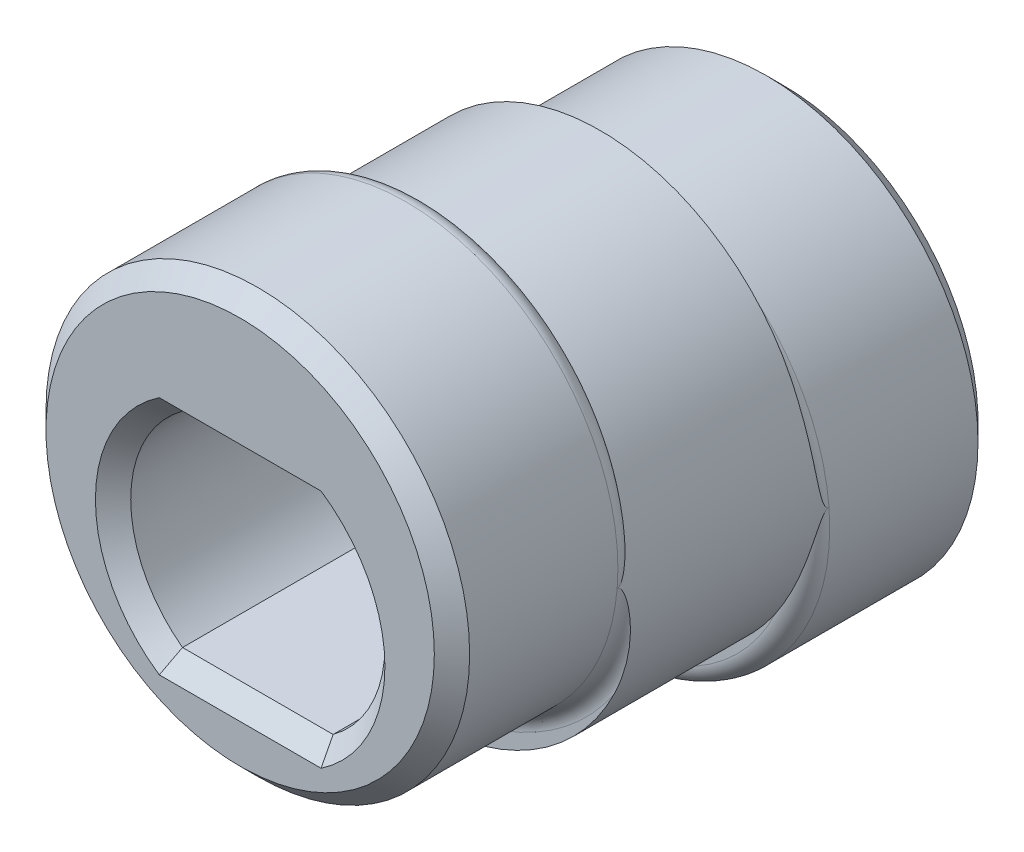
SolidWorks part; units mm, degrees
material "Polylactic Acid (PLA)"
ref_plane "Front Plane" through (0, 0, 0) normal (0, 0, 1) x (1, 0, 0)
ref_plane "Top Plane" through (0, 0, 0) normal (0, 1, 0) x (1, 0, 0)
ref_plane "Right Plane" through (0, 0, 0) normal (1, 0, 0) x (0, 0, -1)
sketch "Sketch6" plane through (0, 0, 0) normal (0, 0, 1) x (1, 0, 0)
  circle A0 centre (0, 0) radius 6
  dimension "D1" = 12
extrude "Boss-Extrude4" add sketch "Sketch6" along normal mid plane 5
sketch "Sketch7" plane through (0, 0, 2.5) normal (0, 0, 1) x (1, 0, 0)
  circle A0 centre (0, 1) radius 6
  dimension "D1" = 12
  dimension "D2" = 1
extrude "Boss-Extrude5" add sketch "Sketch7" along normal blind 5.2
sketch "Sketch8" plane through (0, 0, -2.5) normal (0, 0, -1) x (-1, 0, 0)
  circle A0 centre (0, -1) radius 6
  dimension "D1" = 12
  dimension "D2" = 1
extrude "Boss-Extrude6" add sketch "Sketch8" along normal blind 5.2
sketch "Sketch11" plane through (0, 0, 2.5) normal (0, 0, 1) x (1, 0, 0)
  line L0 (-2.1331, -2.9) -> (2.1331, -2.9)
  line L1 (-1.9975, -2.5) -> (1.9975, -2.5) construction
  line L2 (-1.9975, -2.5) -> (-1.9975, 2.5) construction
  line L3 (-1.9975, 2.5) -> (1.9975, 2.5) construction
  line L4 (1.9975, -2.5) -> (1.9975, 2.5) construction
  line L5 (-1.9975, -2.5) -> (1.9975, 2.5) construction
  line L6 (-1.9975, 2.5) -> (1.9975, -2.5) construction
  line L7 (-2.1331, 2.9) -> (2.1331, 2.9)
  arc A0 (-1.9975, 2.5) -> (-1.9975, -2.5) centre (0, 0) ccw construction
  arc A1 (1.9975, -2.5) -> (1.9975, 2.5) centre (0, 0) ccw construction
  arc A2 (2.1331, -2.9) -> (2.1331, 2.9) centre (0, 0) ccw
  arc A3 (-2.1331, 2.9) -> (-2.1331, -2.9) centre (0, 0) ccw
  dimension "D1" = 6.4
  dimension "D2" = 2.5
  dimension "D3" = 0.4
extrude "Cut-Extrude1" cut sketch "Sketch11" against normal through all both and the other way through all
fillet "Fillet1" radius 0.5 2 edges at (0, -5, 2.5) (0, 5, -2.5)
fillet "Fillet2" radius 0.5 2 edges at (0, -7, -2.5) (0, 7, 2.5)
chamfer "Chamfer1" distance 0.5 angle 45 2 edges at (-6, -1, -7.7) (6, 1, 7.7)
chamfer "Chamfer2" distance 0.5 angle 45 8 edges at (0, -2.9, -7.7) (3.6, 0, -7.7) (-3.6, 0, -7.7) (0, 2.9, -7.7) (-3.6, 0, 7.7) (0, -2.9, 7.7) (3.6, 0, 7.7) (0, 2.9, 7.7)
